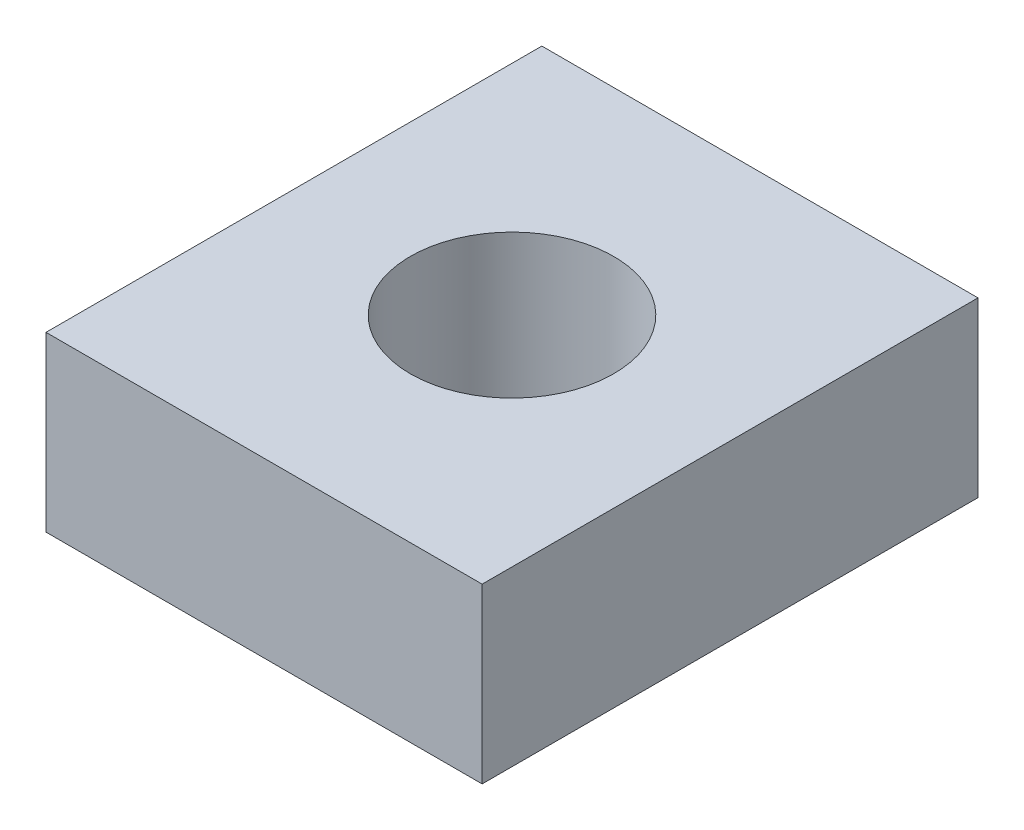
SolidWorks part; units mm, degrees
ref_plane "Front Plane" through (0, 0, 0) normal (0, 0, 1) x (1, 0, 0)
ref_plane "Top Plane" through (0, 0, 0) normal (0, 1, 0) x (1, 0, 0)
ref_plane "Right Plane" through (0, 0, 0) normal (1, 0, 0) x (0, 0, -1)
sketch "Sketch1" plane through (0, 0, 0) normal (0, 1, 0) x (1, 0, 0)
  line L1 (-5.4737, 6.223) -> (5.4737, 6.223)
  line L2 (-5.4737, 6.223) -> (-5.4737, -6.223)
  line L3 (-5.4737, -6.223) -> (5.4737, -6.223)
  line L4 (5.4737, 6.223) -> (5.4737, -6.223)
  line L5 (-5.4737, 6.223) -> (5.4737, -6.223) construction
  line L6 (-5.4737, -6.223) -> (5.4737, 6.223) construction
  point P0 (0, 0)
  dimension "D1" = 12.446
  dimension "D2" = 10.9474
extrude "Boss-Extrude1" add sketch "Sketch1" along normal blind 4.3434
hole_wizard "1/4-20 Tapped Hole1" positions "Sketch2" profile "Sketch3" tap size "1/4-20" standard "ANSI Inch" end condition through all
sketch "Sketch2" plane through (0, 4.3434, 0) normal (0, 1, 0) x (1, 0, 0)
  point P0 (0, 0)
cosmetic thread "Hole Thread1" parameters "D2"=6.35
sketch "Sketch3" plane through (0, 4.3434, 0) normal (1, 0, 0) x (0, 0, 1)
  line L0 (0, 0) -> (0, 4.3434)
  line L1 (0, 4.3434) -> (2.5527, 4.3434)
  line L2 (2.5527, 4.3434) -> (2.5527, 0)
  line L5 (2.5527, 0) -> (0, 0)
  line L11 (0, -6.35) -> (0, 107.95) construction
  dimension "Thru Tap Drill Dia." = 5.1054
  dimension "Thru Tap Drill Depth" = 4.3434
